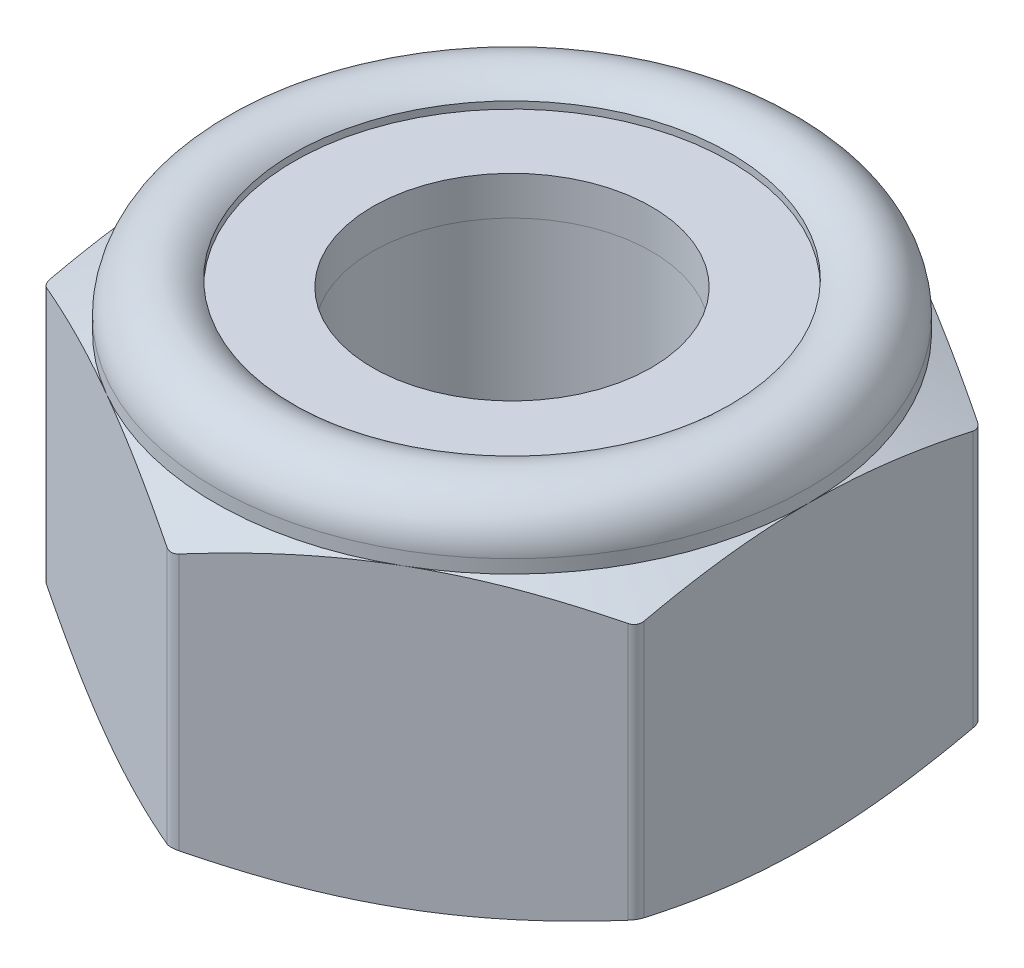
SolidWorks part; units mm, degrees
material "Chrome Stainless Steel"
ref_plane "Front Plane" through (0, 0, 0) normal (0, 0, 1) x (1, 0, 0)
ref_plane "Top Plane" through (0, 0, 0) normal (0, 1, 0) x (1, 0, 0)
ref_plane "Right Plane" through (0, 0, 0) normal (1, 0, 0) x (0, 0, -1)
sketch "Sketch1" plane through (0, 0, 0) normal (0, 0, 1) x (1, 0, 0)
  line L0 (0, -3) -> (0, 3) construction
  line L1 (5, 0) -> (-5, 0) construction
  line L2 (3, -3) -> (-3, -3) construction
  line L3 (3, -3) -> (3, -2) construction
  point P4 (0, 0)
  point P8 (0, 0)
  point P11 (0, -3)
  dimension "Height" = 6
  dimension "Width" = 10
  dimension "Thread Size" = 6
  dimension "Thread Pitch" = 1
sketch "Sketch2" plane through (0, 0, 0) normal (0, 1, 0) x (1, 0, 0)
  line L0 (-3, 0.4375) -> (-3, -0.4375) construction
  line L1 (0, 5.7735) -> (-5, 2.8868)
  line L2 (-5, 2.8868) -> (-5, -2.8868)
  line L3 (-5, -2.8868) -> (0, -5.7735)
  line L4 (0, -5.7735) -> (5, -2.8868)
  line L5 (5, -2.8868) -> (5, 2.8868)
  line L6 (5, 2.8868) -> (0, 5.7735)
  line L7 (-3, -0.4375) -> (-2.3505, -0.0625) construction
  line L8 (-2.3505, -0.0625) -> (-2.3505, 0.0625) construction
  line L9 (-2.3505, 0.0625) -> (-3, 0.4375) construction
  line L10 (-2.3505, 0) -> (-3, 0) construction
  line L11 (-2.6752, 0.25) -> (-2.6752, -0.25) construction
  line L12 (3, 0) -> (-3, 0) construction
  line L13 (5, 0) -> (-5, 0) construction
  circle A0 centre (0, 0) radius 5 construction
  circle A1 centre (0, 0) radius 2.3505
  point P19 (0, -2.3505)
  dimension "D1" = 0.125
  dimension "D2" = 0.5
  dimension "D3" = 60
extrude "Boss-Extrude1" add sketch "Sketch2" along normal up to vertex (3 mm away) and the other way up to vertex (3 mm away) up to point (0, 3, 0) other way up to point (0, -3, 0)
fillet "Fillet1" radius 0.2 6 edges at (-5, 0, -2.8868) (0, 0, -5.7735) (-5, 0, 2.8868) (5, 0, -2.8868) (5, 0, 2.8868) (0, 0, 5.7735)
sketch "Sketch3" plane through (0, 0, 0) normal (1, 0, 0) x (0, 0, -1)
  line L0 (5.7735, 2) -> (5.7735, 4)
  line L2 (5, -3) -> (5.7735, -2.6393)
  line L3 (2.9445, -3) -> (5.7158, -3) construction
  line L4 (5.7735, 3) -> (5.7735, -3) construction
  line L5 (5.7735, -2.6393) -> (5.7735, -3)
  line L6 (5.7735, -3) -> (5, -3)
  line L7 (5, 2) -> (5.7735, 1.6393)
  line L8 (5.7735, 1.6393) -> (5.7735, 2)
  line L11 (5, 2) -> (5, 2.224)
  line L12 (2.9445, 3) -> (5.7158, 3) construction
  line L13 (2.3505, 2) -> (3.6752, 2)
  line L14 (3.6752, 2) -> (3.6752, 2.7727)
  line L15 (3.6752, 2) -> (5, 2) construction
  line L16 (3.6752, 2.7727) -> (4.224, 2.224) construction
  line L17 (4.224, 2.224) -> (4.224, 3) construction
  line L18 (2.3505, 2) -> (2.3505, 4)
  line L19 (2.3505, 4) -> (5.7735, 4)
  line L21 (2.3505, -3) -> (2.3505, -2.4)
  line L22 (-2.7713, -3) -> (2.7713, -3) construction
  line L24 (2.9505, -3) -> (2.3505, -3)
  line L25 (2.3505, -2.4) -> (2.9505, -3)
  arc A0 (5, 2.224) -> (3.6752, 2.7727) centre (4.224, 2.224) ccw
  point P0 (5, 2)
  point P1 (5, 0)
  point P14 (2.3505, 0)
  dimension "D1" = 5
  dimension "D2" = 25
  dimension "D3" = 45
  dimension "D4" = 1
  dimension "D5" = 0.6
revolve "Cut-Revolve2" cut sketch "Sketch3" angle 360 about L0
sketch "Sketch4" plane through (0, 0, 0) normal (1, 0, 0) x (0, 0, -1)
  line L0 (-3.6752, 2.7727) -> (-3.6752, 2) construction
  line L1 (-2.3505, 2) -> (-3.6752, 2)
  line L2 (-2.3505, 2) -> (-2.3505, 2.6527)
  line L3 (-2.3505, 2.6527) -> (-3.6752, 2.6527)
  line L4 (-3.6752, 2) -> (-3.6752, 2.6527)
  line L5 (3.6752, 2.7727) -> (-3.6752, 2.7727) construction
  line L6 (2.3505, 2) -> (-2.3505, 2) construction
  dimension "D1" = 0.12
revolve "Revolve1" add sketch "Sketch4" angle 360 about L0
sketch "Sketch5" plane through (0, 0, 0) normal (0, 1, 0) x (1, 0, 0)
  circle A0 centre (0, 0) radius 2.3505 construction
  point P0 (0, -2.3505)
sketch "Sketch6" [suppressed] plane through (0, 0, 0) normal (0, 0, 1) x (1, 0, 0)
  line L0 (3, 2) -> (3, -3)
  line L2 (0, -3) -> (5, -3) construction
  line L3 (3, -3) -> (0, -3)
  line L4 (0, -3) -> (0, 2)
  line L5 (0, -3) -> (0, 3) construction
  line L6 (0, 2) -> (3, 2)
  line L7 (5, 2) -> (2.5, 2) construction
revolve "Revolve2" [suppressed] add sketch "Sketch6" angle 360 about L4
sketch "Sketch7" [suppressed] plane through (0, -3, 0) normal (0, -1, 0) x (1, 0, 0)
  circle A2 centre (0, 0) radius 3
  circle A3 centre (0, 0) radius 3
  dimension "D1" = 0
curve "Helix/Spiral1" [suppressed] pitch 1 height 6 turns 6
sketch "Sketch8" [suppressed] plane through (0, 0, 0) normal (0, 0, 1) x (1, 0, 0)
  line L0 (3.1083, -2.9375) -> (2.2422, -3.4375) construction
  line L1 (2.2422, -3.4375) -> (3.1083, -3.9375) construction
  line L2 (3.1083, -3.9375) -> (3.1083, -2.9375) construction
  line L3 (2.3505, -3.375) -> (2.3505, -3.5)
  line L4 (3, -3) -> (3, -3.875) construction
  line L5 (3, -3.4375) -> (3.1083, -3.4375) construction
  line L6 (2.2422, -3.4375) -> (2.3505, -3.4375) construction
  line L7 (3.0541, -3.4375) -> (3.0541, -3.9062) construction
  line L8 (2.3505, -3.375) -> (3.1083, -2.9375)
  line L9 (3.1083, -2.9375) -> (3.0541, -3.9062)
  line L10 (2.3505, -3.5) -> (3.0541, -3.9062)
  dimension "D1" = 1
  dimension "D2" = 0.125
sweep "Cut-Sweep1" [suppressed] cut profiles "Sketch8" path "Helix/Spiral1"
sketch "Sketch9" [suppressed] plane through (0, 0, 0) normal (0, 0, 1) x (1, 0, 0)
  line L0 (0, 0) -> (0, -3)
  line L1 (0, 0) -> (0, 0.6)
  line L2 (0, -3) -> (3, -3)
  line L3 (3, -3) -> (3.6, -3)
  line L4 (3.6, -3) -> (0, 0.6)
  dimension "D1" = 0.6
revolve "Revolve3" [suppressed] add sketch "Sketch9" angle 360 about L0
sketch "Sketch10" [suppressed] plane through (0, -3, 0) normal (0, -1, 0) x (1, 0, 0)
  circle A0 centre (0, 0) radius 2.9505 construction
  circle A1 centre (0, 0) radius 2.9505
extrude "Boss-Extrude2" [suppressed] add sketch "Sketch10" against normal up to surface (5 mm away) up to face at (3.6752, 2, 0)
combine bodies "Combine1" [suppressed] operation type subtract main body 110 bodies to subtract 109
equation "\"D1@Sketch3\"=\"Height@sketch1\"*(5/6)"
equation "\"D5@Sketch3\"=\"Thread Size@Sketch1\"*.1"
equation "\"D4@Helix/Spiral1\"=\"Thread Pitch@sketch1\""
equation "\"D3@Helix/Spiral1\"=\"Height@sketch1\""
equation "\"D1@Sketch8\"=\"Thread Pitch@sketch1\""
equation "\"D2@Sketch8\"=\"Thread Pitch@sketch1\"/8"
equation "\"D1@Sketch9\"=\"Thread Size@Sketch1\" * .1"
equation "\"D1@Sketch2\"=\"Thread Pitch@sketch1\"/8"
equation "\"D2@Sketch2\"=\"Thread Pitch@sketch1\"/2"
equation "\"D1@Sketch4\" = \"Height@Sketch1\" * .02"
equation "\"D1@Fillet1\"=\"Width@sketch1\"*.02"
